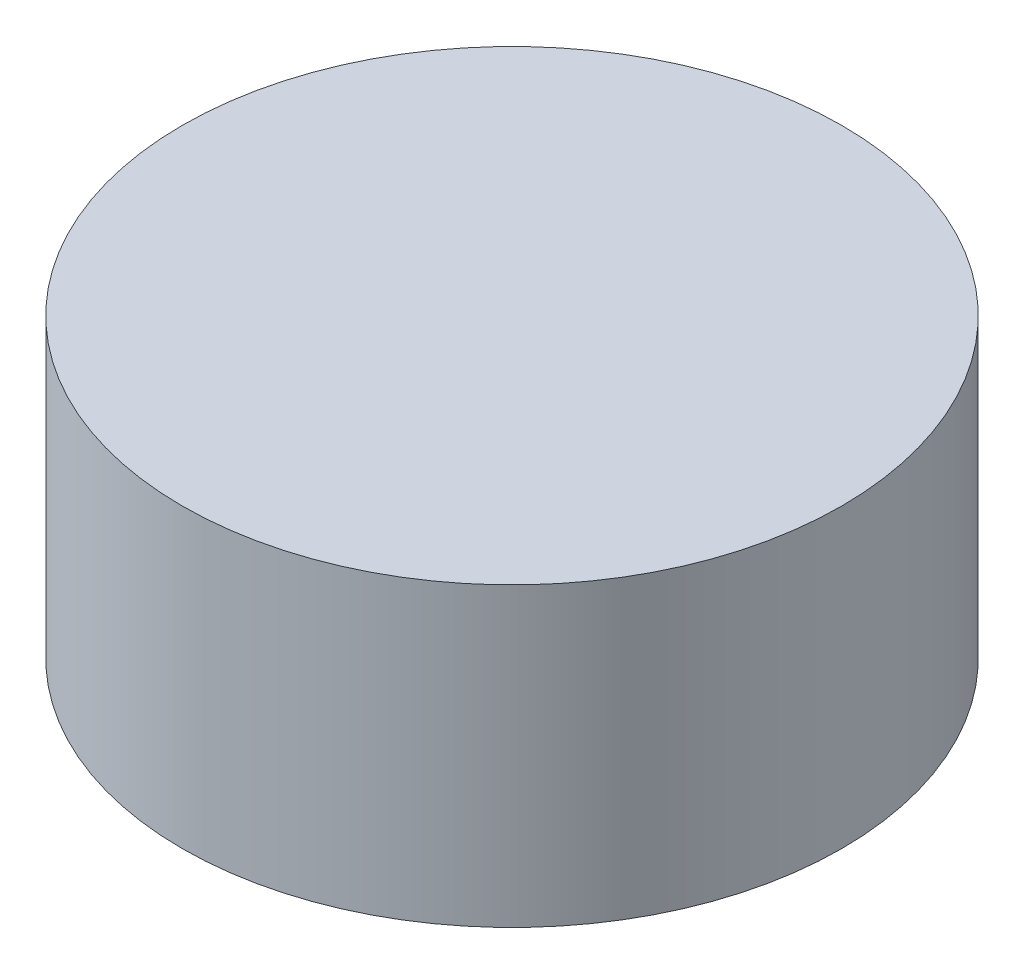
SolidWorks part; units mm, degrees
ref_plane "Front Plane" through (0, 0, 0) normal (0, 0, 1) x (1, 0, 0)
ref_plane "Top Plane" through (0, 0, 0) normal (0, 1, 0) x (1, 0, 0)
ref_plane "Right Plane" through (0, 0, 0) normal (1, 0, 0) x (0, 0, -1)
sketch "Sketch1" plane through (0, 0, 0) normal (0, 1, 0) x (1, 0, 0)
  circle A0 centre (0, 0) radius 25.4
  dimension "D1" = 50.8
extrude "Boss-Extrude1" add sketch "Sketch1" along normal blind 22.86
ref_axis "Axis1" through (0, 26.67, 0) along (0, -1, 0)
